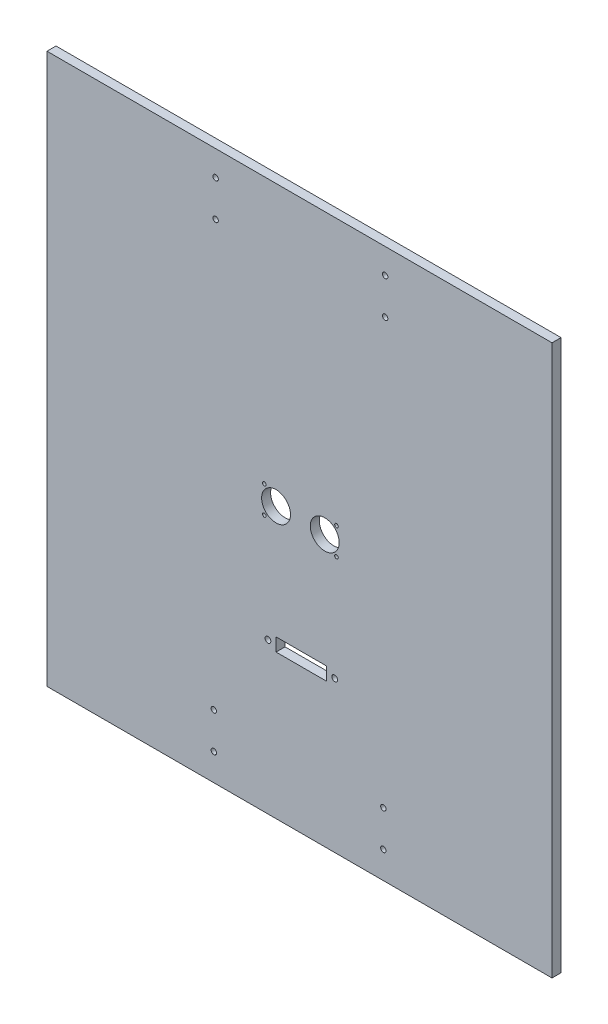
SolidWorks part; units mm, degrees
ref_plane "Plan de face" through (0, 0, 0) normal (0, 0, 1) x (1, 0, 0)
ref_plane "Plan de dessus" through (0, 0, 0) normal (0, 1, 0) x (1, 0, 0)
ref_plane "Plan de droite" through (0, 0, 0) normal (1, 0, 0) x (0, 0, -1)
sketch "Esquisse1" plane through (0, 0, 0) normal (0, 0, 1) x (1, 0, 0)
  line L1 (0, 0) -> (280, 0)
  line L2 (0, 0) -> (0, 305)
  line L3 (0, 305) -> (280, 305)
  line L4 (280, 0) -> (280, 305)
  dimension "D1" = 305
  dimension "D2" = 280
extrude "Boss.-Extru.1" add sketch "Esquisse1" along normal blind 5
sketch "Esquisse2" plane through (0, 0, 5) normal (0, 0, 1) x (1, 0, 0)
  circle A0 centre (92.5, 35) radius 1.5
  circle A1 centre (92.5, 15) radius 1.5
  circle A2 centre (186.5, 35) radius 1.5
  circle A3 centre (186.5, 15) radius 1.5
  dimension "D1" = 3
  dimension "D2" = 3
  dimension "D3" = 3
  dimension "D4" = 3
extrude "Enlèv. mat.-Extru.1" cut sketch "Esquisse2" against normal through all
sketch "Esquisse3" plane through (0, 0, 5) normal (0, 0, 1) x (1, 0, 0)
  circle A0 centre (187.5, 271.0376) radius 1.5
  circle A1 centre (187.5, 291.0376) radius 1.5
  circle A2 centre (93.5, 271.0376) radius 1.5
  circle A3 centre (93.5, 291.0376) radius 1.5
  circle A4 centre (187.5, 291.0376) radius 1.5 construction
  dimension "D1" = 3
  dimension "D2" = 3
  dimension "D3" = 3
  dimension "D4" = 3
  dimension "D5" = 0
extrude "Enlèv. mat.-Extru.2" cut sketch "Esquisse3" against normal through all
sketch "Esquisse4" plane through (0, 0, 0) normal (0, 0, -1) x (-1, 0, 0)
  line L0 (0, 0) -> (-280, 0) construction
  line L1 (-155, 87.3) -> (-127, 87.3)
  line L2 (-155, 87.3) -> (-155, 80)
  line L3 (-155, 80) -> (-127, 80)
  line L4 (-127, 87.3) -> (-127, 80)
  line L5 (-280, 0) -> (-280, 305) construction
  line L6 (-180.5491, 83.65) -> (-87.7218, 83.65) construction
  circle A0 centre (-159.5, 83.65) radius 1.6
  circle A1 centre (-122.5, 83.65) radius 1.6
  point P4 (-141, 80)
  point P9 (-155, 83.65)
  dimension "D6" = 3.2
  dimension "D7" = 3.2
  dimension "D8" = 4.5
  dimension "D1" = 7.3
  dimension "D2" = 28
  dimension "D3" = 80
  dimension "D4" = 125
  dimension "D5" = 3.65
  dimension "D9" = 4.5
extrude "Enlèv. mat.-Extru.3" cut sketch "Esquisse4" against normal through all
sketch "Esquisse5" plane through (0, 0, 0) normal (0, 0, -1) x (-1, 0, 0)
  line L0 (0, 305) -> (0, 0) construction
  line L2 (0, 0) -> (-280, 0) construction
  circle A0 centre (-154, 150) radius 8
  circle A1 centre (-127, 150) radius 8
  circle A2 centre (-160.5026, 157.4915) radius 1
  circle A3 centre (-120.5026, 157.5151) radius 1
  circle A4 centre (-120.4988, 142.502) radius 1
  circle A5 centre (-160.4988, 142.4915) radius 1
  dimension "D1" = 16
  dimension "D2" = 16
  dimension "D3" = 27
  dimension "D4" = 127
  dimension "D5" = 150
  dimension "D6" = 150
  dimension "D7" = 2
  dimension "D8" = 2
  dimension "D9" = 2
  dimension "D10" = 2
  dimension "D11" = 40
  dimension "D12" = 15
  dimension "D13" = 34.33
  dimension "D14" = 34.33
  dimension "D15" = 34.33
  dimension "D16" = 34.33
  dimension "D17" = 40
  dimension "D18" = 9.92
extrude "Enlèv. mat.-Extru.4" cut sketch "Esquisse5" against normal through all
